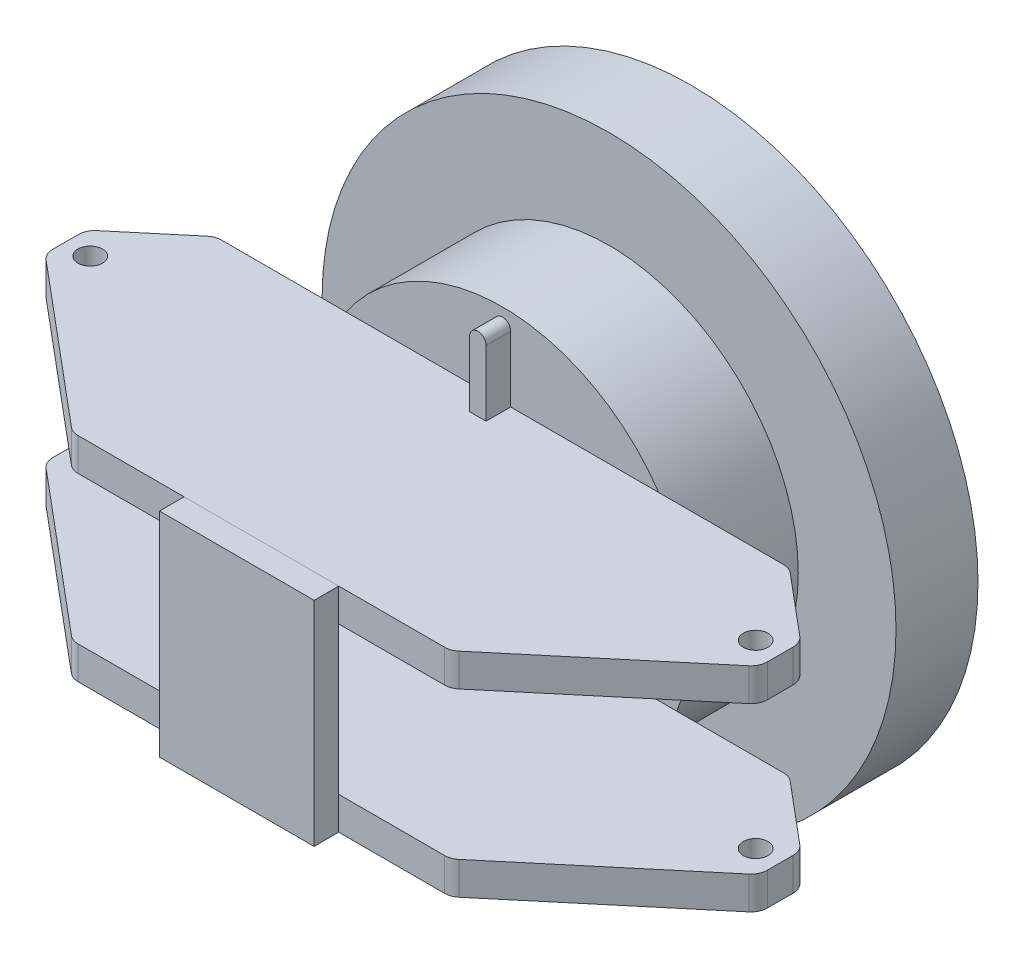
SolidWorks part; units mm, degrees
material "AISI 347 Annealed Stainless Steel (SS)"
ref_plane "Front" through (0, 0, 0) normal (0, 0, 1) x (1, 0, 0)
ref_plane "Top" through (0, 0, 0) normal (0, 1, 0) x (1, 0, 0)
ref_plane "Right" through (0, 0, 0) normal (1, 0, 0) x (0, 0, -1)
sketch "Sketch1" plane through (0, 0, 0) normal (0, 0, 1) x (1, 0, 0)
  circle A0 centre (0, 0) radius 35
  dimension "D1" = 70
extrude "Boss-Extrude1" add sketch "Sketch1" along normal blind 10
sketch "Sketch2" plane through (0, 0, 10) normal (0, 0, 1) x (1, 0, 0)
  circle A0 centre (0, 0) radius 23.08
extrude "Boss-Extrude2" add sketch "Sketch2" along normal blind 13 contours A0
ref_plane "Plane1" through (0, 13, 0) normal (0, 1, 0) x (1, 0, 0)
sketch "Sketch4" plane through (0, 13, 0) normal (0, 1, 0) x (1, 0, 0)
  line L0 (0, -23) -> (-48.9101, -23) construction
  line L1 (-23.08, -23) -> (23.08, -23) construction
  line L2 (35, -23) -> (-35, -23)
  line L3 (-35, -23) -> (-43.5797, -30.1992)
  line L4 (-43.5797, -30.1992) -> (-43.5797, -35.1992)
  line L5 (-23.08, -23) -> (-23.08, -83.02) construction
  line L6 (-23.08, -10) -> (-23.08, -23) construction
  line L7 (-43.5797, -35.1992) -> (-23.08, -52.4005)
  line L8 (-43.5797, -35.1992) -> (-43.5797, -54.4246) construction
  line L9 (-23.08, -52.4005) -> (23.08, -52.4005)
  line L10 (0, -23) -> (0, -50.8219) construction
  line L11 (43.5797, -35.1992) -> (23.08, -52.4005)
  line L12 (43.5797, -30.1992) -> (43.5797, -35.1992)
  line L13 (35, -23) -> (43.5797, -30.1992)
  point P17 (0, -52.4005)
  dimension "D1" = 35
  dimension "D2" = 40
  dimension "D3" = 5
  dimension "D4" = 11.2
  dimension "D5" = 50
extrude "Boss-Extrude3" add sketch "Sketch4" against normal blind 4
fillet "Fillet1" radius 2 8 edges at (-35, 11, 23) (35, 11, 23) (43.5797, 11, 30.1992) (43.5797, 11, 35.1992) (23.08, 11, 52.4005) (-23.08, 11, 52.4005) (-43.5797, 11, 35.1992) (-43.5797, 11, 30.1992)
sketch "Sketch5" plane through (0, 13, 0) normal (0, 1, 0) x (1, 0, 0)
  line L0 (-43.5797, -32.6992) -> (-40.5797, -32.6992) construction
  line L1 (-43.5797, -31.1318) -> (-43.5797, -34.2666) construction
  circle A0 centre (-40.5797, -32.6992) radius 1.5
  dimension "D2" = 3
  dimension "D1" = 3
extrude "Cut-Extrude1" cut sketch "Sketch5" against normal blind 4
mirror "Mirror1" about plane through (0, 0, 0) normal (1, 0, 0) of "Cut-Extrude1"
mirror "Mirror2" about plane through (0, 0, 0) normal (0, 1, 0) of "Mirror1", "Cut-Extrude1", "Fillet1", "Boss-Extrude3"
sketch "Sketch6" plane through (0, 0, 23) normal (0, 0, 1) x (1, 0, 0)
  line L0 (0, 23.08) -> (0, 13) construction
  line L1 (19.0706, 13) -> (-19.0706, 13) construction
  line L2 (1, 13) -> (-1, 13)
  line L3 (-1, 13) -> (-1, 22)
  line L4 (-1, 22) -> (1, 22)
  line L5 (1, 13) -> (1, 22)
  arc A0 (19.0706, 13) -> (-19.0706, 13) centre (0, 0) ccw construction
  point P12 (0, 22)
  dimension "D1" = 1
  dimension "D2" = 9
extrude "Boss-Extrude4" add sketch "Sketch6" along normal blind 3
fillet "Fillet2" 2 edges at (1, 22, 24.5) (-1, 22, 24.5) type full round first side face at (1, 17.5, 24.5) second side face at (-1, 17.5, 24.5) middle face at (0, 22, 24.5)
mirror "Mirror3" about plane through (0, 0, 0) normal (0, 1, 0) of "Fillet2", "Boss-Extrude4"
sketch "Sketch7" plane through (0, 0, 52.4005) normal (0, 0, 1) x (1, 0, 0)
  line L0 (-1, 13) -> (-19.0706, 13) construction
  line L1 (9.43, -13) -> (-9.43, -13)
  line L2 (9.43, -13) -> (9.43, 13)
  line L3 (9.43, 13) -> (-9.43, 13)
  line L4 (-9.43, -13) -> (-9.43, 13)
  line L5 (9.43, -13) -> (-9.43, 13) construction
  line L6 (9.43, 13) -> (-9.43, -13) construction
  point P0 (0, 0)
extrude "Boss-Extrude5" add sketch "Sketch7" along normal blind 3 separate body
sketch "Sketch8" plane through (0, 0, 0) normal (0, 0, -1) x (-1, 0, 0)
  circle A0 centre (0, 0) radius 10
  dimension "D1" = 20
extrude "Cut-Extrude2" cut sketch "Sketch8" against normal blind 10
